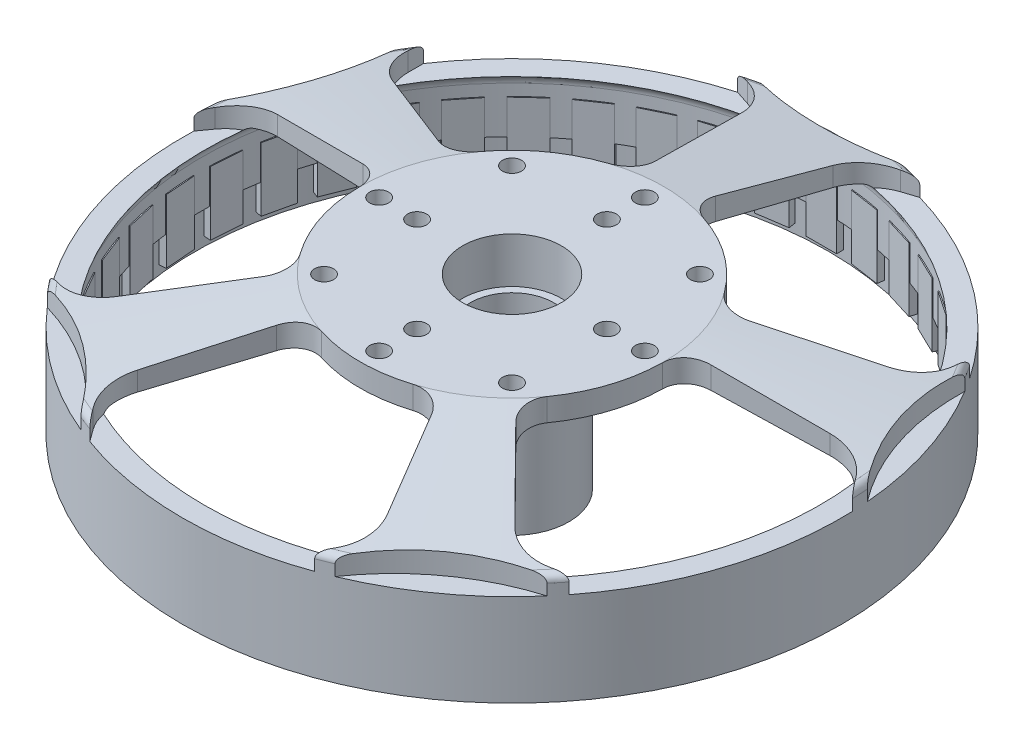
SolidWorks part; units mm, degrees
ref_plane "Front Plane" through (0, 0, 0) normal (0, 0, 1) x (1, 0, 0)
ref_plane "Top Plane" through (0, 0, 0) normal (0, 1, 0) x (1, 0, 0)
ref_plane "Right Plane" through (0, 0, 0) normal (1, 0, 0) x (0, 0, -1)
sketch "Sketch2" plane through (0, 0, 0) normal (0, 0, 1) x (1, 0, 0)
  line L0 (0, 0) -> (0, -18.25) construction
  line L1 (0, -18.25) -> (43.4, -18.25) construction
  line L2 (43.4, -18.25) -> (43.4, -6.1)
  line L3 (20, -3) -> (8.5, -3)
  line L4 (40.9, -5.8) -> (40.9, -13.25)
  line L5 (40.9, -13.25) -> (41.7, -13.25)
  line L6 (41.7, -13.25) -> (41.7, -18.25)
  line L7 (41.7, -18.25) -> (43.4, -18.25)
  line L8 (20, 0) -> (6.5, 0)
  line L9 (20, 0) -> (43.4, -3.8)
  line L10 (43.4, -3.8) -> (43.4, -6.1)
  line L12 (8.5, -3) -> (8.5, -8)
  line L13 (20, -3) -> (40.9, -5.8)
  line L14 (8.5, -8) -> (7.5, -8)
  line L15 (7.5, -8) -> (7.5, -24.5)
  line L16 (7.5, -24.5) -> (3.5, -24.5)
  line L17 (3.5, -24.5) -> (3.5, -19.5)
  line L18 (3.5, -19.5) -> (5.5, -19.5)
  line L19 (5.5, -19.5) -> (5.5, -6)
  line L20 (5.5, -6) -> (6.5, -6)
  line L21 (6.5, -6) -> (6.5, 0)
  dimension "D1" = 18.25
  dimension "D2" = 43.4
  dimension "D3" = 12.15
  dimension "D4" = 1.7
  dimension "D5" = 5
  dimension "D6" = 2.5
  dimension "D7" = 3
  dimension "D8" = 2.3
  dimension "D9" = 20
  dimension "D10" = 2
  dimension "D11" = 24.5
  dimension "D12" = 7.5
  dimension "D13" = 3.5
  dimension "D14" = 5.5
  dimension "D15" = 6.5
  dimension "D16" = 8.5
  dimension "D17" = 6
  dimension "D18" = 5
  dimension "D19" = 19.5
revolve "Revolve1" add sketch "Sketch2" angle 360 about L0
fillet "Fillet1" radius 1 1 edges at (0, -3.8, 43.4)
fillet "Fillet2" radius 1.5 1 edges at (0, -5.8, 40.9)
fillet "Fillet3" radius 0.5 1 edges at (0, -19.5, 5.5)
sketch "Sketch3" plane through (0, 0, 0) normal (0, 1, 0) x (1, 0, 0)
  line L0 (0, 0) -> (0, -43.4) construction
  line L1 (0, 0) -> (-25.5099, -35.1113) construction
  line L2 (0, 0) -> (-41.2759, -13.4113) construction
  line L3 (0, 0) -> (-41.2759, 13.4113) construction
  line L4 (0, 0) -> (-25.5099, 35.1113) construction
  line L5 (0, 0) -> (0, 43.4) construction
  line L6 (0, 0) -> (25.5099, 35.1113) construction
  line L7 (0, 0) -> (41.2759, 13.4113) construction
  line L8 (0, 0) -> (41.2759, -13.4113) construction
  line L9 (0, 0) -> (25.5099, -35.1113) construction
  line L10 (7, 42.8318) -> (3.5, 19.6914) construction
  line L11 (17.646, 9.4137) -> (38.5723, 19.8931) construction
  line L12 (3.9727, 22.8168) -> (6.0087, 36.2774)
  line L13 (20.4724, 10.8291) -> (32.6451, 16.9249)
  line L14 (10.0871, 41.0865) -> (12, 41.708)
  line L15 (35.9585, 22.2898) -> (35.9585, 24.3012)
  line L16 (22.9277, 3.2725) -> (36.3587, 5.4958)
  line L17 (16.6254, -16.1241) -> (26.1845, -25.8173)
  line L18 (42.1926, 3.103) -> (43.3749, 1.4758)
  line L19 (32.3106, -27.3106) -> (34.2236, -26.6891)
  line L20 (10.1974, -20.7943) -> (16.4622, -32.8809)
  line L21 (-10.1974, -20.7943) -> (-16.4622, -32.8809)
  line L22 (15.9894, -39.1687) -> (14.8072, -40.7959)
  line L23 (-15.9894, -39.1687) -> (-14.8072, -40.7959)
  line L24 (-16.6254, -16.1241) -> (-26.1845, -25.8173)
  line L25 (-22.9277, 3.2725) -> (-36.3587, 5.4958)
  line L26 (-32.3106, -27.3106) -> (-34.2236, -26.6891)
  line L27 (-42.1926, 3.103) -> (-43.3749, 1.4758)
  line L28 (-20.4724, 10.8291) -> (-32.6451, 16.9249)
  line L29 (-3.9727, 22.8168) -> (-6.0087, 36.2774)
  line L30 (-35.9585, 22.2898) -> (-35.9585, 24.3012)
  line L31 (-10.0871, 41.0865) -> (-12, 41.708)
  circle A0 centre (0, 0) radius 43.4 construction
  arc A1 (3.5, 19.6914) -> (17.646, 9.4137) centre (0, 0) cw construction
  arc A3 (7, 42.8318) -> (38.5723, 19.8931) centre (0, 0) cw construction
  arc A4 (6.3263, 18.9731) -> (16.0896, 11.8796) centre (0, 0) cw
  arc A5 (6.3263, 18.9731) -> (3.9727, 22.8168) centre (7.4334, 22.2934) cw
  arc A6 (16.0896, 11.8796) -> (20.4724, 10.8291) centre (18.9052, 13.9586) ccw
  arc A7 (6.0087, 36.2774) -> (10.0871, 41.0865) centre (11.9412, 35.3801) cw
  arc A8 (32.6451, 16.9249) -> (35.9585, 22.2898) centre (29.9585, 22.2898) ccw
  arc A9 (12, 41.708) -> (35.9585, 24.3012) centre (0, 0) cw
  arc A10 (19.9994, -0.1536) -> (16.2702, -11.6311) centre (0, 0) cw
  arc A11 (16.2702, -11.6311) -> (16.6254, -16.1241) centre (19.1174, -13.6665) ccw
  arc A12 (36.3587, 5.4958) -> (42.1926, 3.103) centre (37.3385, -0.4237) cw
  arc A13 (26.1845, -25.8173) -> (32.3106, -27.3106) centre (30.4565, -21.6043) ccw
  arc A14 (43.3749, 1.4758) -> (34.2236, -26.6891) centre (0, 0) cw
  arc A15 (19.9994, -0.1536) -> (22.9277, 3.2725) centre (23.4993, -0.1805) cw
  arc A16 (6.034, -19.068) -> (-6.034, -19.068) centre (0, 0) cw
  arc A17 (-6.034, -19.068) -> (-10.1974, -20.7943) centre (-7.09, -22.405) ccw
  arc A18 (16.4622, -32.8809) -> (15.9894, -39.1687) centre (11.1353, -35.642) cw
  arc A19 (-16.4622, -32.8809) -> (-15.9894, -39.1687) centre (-11.1353, -35.642) ccw
  arc A20 (14.8072, -40.7959) -> (-14.8072, -40.7959) centre (0, 0) cw
  arc A21 (6.034, -19.068) -> (10.1974, -20.7943) centre (7.09, -22.405) cw
  arc A22 (-16.2702, -11.6311) -> (-19.9994, -0.1536) centre (0, 0) cw
  arc A23 (-19.9994, -0.1536) -> (-22.9277, 3.2725) centre (-23.4993, -0.1805) ccw
  arc A24 (-26.1845, -25.8173) -> (-32.3106, -27.3106) centre (-30.4565, -21.6043) cw
  arc A25 (-36.3587, 5.4958) -> (-42.1926, 3.103) centre (-37.3385, -0.4237) ccw
  arc A26 (-34.2236, -26.6891) -> (-43.3749, 1.4758) centre (0, 0) cw
  arc A27 (-16.2702, -11.6311) -> (-16.6254, -16.1241) centre (-19.1174, -13.6665) cw
  arc A28 (-16.0896, 11.8796) -> (-6.3263, 18.9731) centre (0, 0) cw
  arc A29 (-6.3263, 18.9731) -> (-3.9727, 22.8168) centre (-7.4334, 22.2934) ccw
  arc A30 (-32.6451, 16.9249) -> (-35.9585, 22.2898) centre (-29.9585, 22.2898) cw
  arc A31 (-6.0087, 36.2774) -> (-10.0871, 41.0865) centre (-11.9412, 35.3801) ccw
  arc A32 (-35.9585, 24.3012) -> (-12, 41.708) centre (0, 0) cw
  arc A33 (-16.0896, 11.8796) -> (-20.4724, 10.8291) centre (-18.9052, 13.9586) cw
  circle A34 centre (0, 0) radius 20 construction
  point P17 (0, 0)
  point P95 (0, 0)
  dimension "D4" = 3.5
  dimension "D5" = 6
  dimension "D2" = 3.5
  dimension "D3" = 7
  dimension "D6" = 12
  dimension "D1" = 10
  dimension "D7" = 5
extrude "Cut-Extrude2" cut sketch "Sketch3" against normal offset from surface (6.1 mm away) 12.15 up to face at (0, -18.25, 43.4)
sketch "Sketch4" plane through (0, 0, 0) normal (0, 1, 0) x (1, 0, 0)
  line L0 (0, 0) -> (0, 70.5165) construction
  line L1 (-10, 42.2322) -> (10, 42.2322) construction
  line L2 (0, 0) -> (67.0652, 21.7908) construction
  line L3 (0, 0) -> (41.4486, -57.049) construction
  line L4 (0, 0) -> (-41.4486, -57.049) construction
  line L5 (0, 0) -> (-67.0652, 21.7908) construction
  circle A0 centre (0, 70.5165) radius 30
  arc A1 (-34.2236, 26.6891) -> (-12, 41.708) centre (0, 0) ccw construction
  circle A2 centre (67.0652, 21.7908) radius 30
  circle A3 centre (41.4486, -57.049) radius 30
  circle A4 centre (-41.4486, -57.049) radius 30
  circle A5 centre (-67.0652, 21.7908) radius 30
  point P20 (0, 0)
  dimension "D1" = 60
  dimension "D2" = 20
  dimension "D3" = 5
extrude "Cut-Extrude3" cut sketch "Sketch4" against normal offset from surface (6.1 mm away) 12.15 up to face at (0, -18.25, 43.4)
sketch "Sketch6" plane through (0, -13.25, 0) normal (0, -1, 0) x (1, 0, 0)
  line L0 (0, 0) -> (0, -41.202) construction
  line L1 (-4.0961, -40.5949) -> (-8.0514, -39.9988)
  line L2 (2, -40.752) -> (-2, -40.752)
  line L3 (2, -40.752) -> (2, -41.652)
  line L4 (2, -41.652) -> (-2, -41.652) construction
  line L5 (-2, -40.752) -> (-2, -41.652)
  line L6 (2, -40.752) -> (-2, -41.652) construction
  line L7 (2, -41.652) -> (-2, -40.752) construction
  line L8 (-4.0961, -40.5949) -> (-4.2302, -41.4849)
  line L9 (-8.0514, -39.9988) -> (-8.1856, -40.8887)
  line L10 (-4.2302, -41.4849) -> (-8.1856, -40.8887) construction
  line L11 (-4.0961, -40.5949) -> (-8.1856, -40.8887) construction
  line L12 (-4.2302, -41.4849) -> (-8.0514, -39.9988) construction
  line L13 (-10.1007, -39.531) -> (-13.923, -38.352)
  line L14 (-10.1007, -39.531) -> (-10.366, -40.391)
  line L15 (-13.923, -38.352) -> (-14.1883, -39.212)
  line L16 (-10.366, -40.391) -> (-14.1883, -39.212) construction
  line L17 (-10.1007, -39.531) -> (-14.1883, -39.212) construction
  line L18 (-10.366, -40.391) -> (-13.923, -38.352) construction
  line L19 (-15.8797, -37.5841) -> (-19.4836, -35.8485)
  line L20 (-15.8797, -37.5841) -> (-16.2702, -38.3949)
  line L21 (-19.4836, -35.8485) -> (-19.8741, -36.6594)
  line L22 (-16.2702, -38.3949) -> (-19.8741, -36.6594) construction
  line L23 (-15.8797, -37.5841) -> (-19.8741, -36.6594) construction
  line L24 (-16.2702, -38.3949) -> (-19.4836, -35.8485) construction
  line L25 (-21.3039, -34.7975) -> (-24.6089, -32.5443)
  line L26 (-21.3039, -34.7975) -> (-21.8109, -35.5411)
  line L27 (-24.6089, -32.5443) -> (-25.1159, -33.2879)
  line L28 (-21.8109, -35.5411) -> (-25.1159, -33.2879) construction
  line L29 (-21.3039, -34.7975) -> (-25.1159, -33.2879) construction
  line L30 (-21.8109, -35.5411) -> (-24.6089, -32.5443) construction
  line L31 (-26.2523, -31.2337) -> (-29.1845, -28.513)
  line L32 (-26.2523, -31.2337) -> (-26.8645, -31.8934)
  line L33 (-29.1845, -28.513) -> (-29.7967, -29.1727)
  line L34 (-26.8645, -31.8934) -> (-29.7967, -29.1727) construction
  line L35 (-26.2523, -31.2337) -> (-29.7967, -29.1727) construction
  line L36 (-26.8645, -31.8934) -> (-29.1845, -28.513) construction
  line L37 (-30.6142, -26.9721) -> (-33.1082, -23.8448)
  line L38 (-30.6142, -26.9721) -> (-31.3179, -27.5333)
  line L39 (-33.1082, -23.8448) -> (-33.8118, -24.4059)
  line L40 (-31.3179, -27.5333) -> (-33.8118, -24.4059) construction
  line L41 (-30.6142, -26.9721) -> (-33.8118, -24.4059) construction
  line L42 (-31.3179, -27.5333) -> (-33.1082, -23.8448) construction
  line L43 (-34.2923, -22.1081) -> (-36.2923, -18.644)
  line L44 (-34.2923, -22.1081) -> (-35.0717, -22.5581)
  line L45 (-36.2923, -18.644) -> (-37.0717, -19.094)
  line L46 (-35.0717, -22.5581) -> (-37.0717, -19.094) construction
  line L47 (-34.2923, -22.1081) -> (-37.0717, -19.094) construction
  line L48 (-35.0717, -22.5581) -> (-36.2923, -18.644) construction
  line L49 (-37.2043, -16.7501) -> (-38.6657, -13.0266)
  line L50 (-37.2043, -16.7501) -> (-38.0421, -17.0789)
  line L51 (-38.6657, -13.0266) -> (-39.5034, -13.3554)
  line L52 (-38.0421, -17.0789) -> (-39.5034, -13.3554) construction
  line L53 (-37.2043, -16.7501) -> (-39.5034, -13.3554) construction
  line L54 (-38.0421, -17.0789) -> (-38.6657, -13.0266) construction
  line L55 (-39.2852, -11.018) -> (-40.1753, -7.1183)
  line L56 (-39.2852, -11.018) -> (-40.1627, -11.2183)
  line L57 (-40.1753, -7.1183) -> (-41.0527, -7.3186)
  line L58 (-40.1627, -11.2183) -> (-41.0527, -7.3186) construction
  line L59 (-39.2852, -11.018) -> (-41.0527, -7.3186) construction
  line L60 (-40.1627, -11.2183) -> (-40.1753, -7.1183) construction
  line L61 (-40.4886, -5.0398) -> (-40.7875, -1.051)
  line L62 (-40.4886, -5.0398) -> (-41.3861, -5.1071)
  line L63 (-40.7875, -1.051) -> (-41.685, -1.1183)
  line L64 (-41.3861, -5.1071) -> (-41.685, -1.1183) construction
  line L65 (-40.4886, -5.0398) -> (-41.685, -1.1183) construction
  line L66 (-41.3861, -5.1071) -> (-40.7875, -1.051) construction
  line L67 (-40.7875, 1.051) -> (-40.4886, 5.0398)
  line L68 (-40.7875, 1.051) -> (-41.685, 1.1183)
  line L69 (-40.4886, 5.0398) -> (-41.3861, 5.1071)
  line L70 (-41.685, 1.1183) -> (-41.3861, 5.1071) construction
  line L71 (-40.7875, 1.051) -> (-41.3861, 5.1071) construction
  line L72 (-41.685, 1.1183) -> (-40.4886, 5.0398) construction
  line L73 (-40.1753, 7.1183) -> (-39.2852, 11.018)
  line L74 (-40.1753, 7.1183) -> (-41.0527, 7.3186)
  line L75 (-39.2852, 11.018) -> (-40.1627, 11.2183)
  line L76 (-41.0527, 7.3186) -> (-40.1627, 11.2183) construction
  line L77 (-40.1753, 7.1183) -> (-40.1627, 11.2183) construction
  line L78 (-41.0527, 7.3186) -> (-39.2852, 11.018) construction
  line L79 (-38.6657, 13.0266) -> (-37.2043, 16.7501)
  line L80 (-38.6657, 13.0266) -> (-39.5034, 13.3554)
  line L81 (-37.2043, 16.7501) -> (-38.0421, 17.0789)
  line L82 (-39.5034, 13.3554) -> (-38.0421, 17.0789) construction
  line L83 (-38.6657, 13.0266) -> (-38.0421, 17.0789) construction
  line L84 (-39.5034, 13.3554) -> (-37.2043, 16.7501) construction
  line L85 (-36.2923, 18.644) -> (-34.2923, 22.1081)
  line L86 (-36.2923, 18.644) -> (-37.0717, 19.094)
  line L87 (-34.2923, 22.1081) -> (-35.0717, 22.5581)
  line L88 (-37.0717, 19.094) -> (-35.0717, 22.5581) construction
  line L89 (-36.2923, 18.644) -> (-35.0717, 22.5581) construction
  line L90 (-37.0717, 19.094) -> (-34.2923, 22.1081) construction
  line L91 (-33.1082, 23.8448) -> (-30.6142, 26.9721)
  line L92 (-33.1082, 23.8448) -> (-33.8118, 24.4059)
  line L93 (-30.6142, 26.9721) -> (-31.3179, 27.5333)
  line L94 (-33.8118, 24.4059) -> (-31.3179, 27.5333) construction
  line L95 (-33.1082, 23.8448) -> (-31.3179, 27.5333) construction
  line L96 (-33.8118, 24.4059) -> (-30.6142, 26.9721) construction
  line L97 (-29.1845, 28.513) -> (-26.2523, 31.2337)
  line L98 (-29.1845, 28.513) -> (-29.7967, 29.1727)
  line L99 (-26.2523, 31.2337) -> (-26.8645, 31.8934)
  line L100 (-29.7967, 29.1727) -> (-26.8645, 31.8934) construction
  line L101 (-29.1845, 28.513) -> (-26.8645, 31.8934) construction
  line L102 (-29.7967, 29.1727) -> (-26.2523, 31.2337) construction
  line L103 (-24.6089, 32.5443) -> (-21.3039, 34.7975)
  line L104 (-24.6089, 32.5443) -> (-25.1159, 33.2879)
  line L105 (-21.3039, 34.7975) -> (-21.8109, 35.5411)
  line L106 (-25.1159, 33.2879) -> (-21.8109, 35.5411) construction
  line L107 (-24.6089, 32.5443) -> (-21.8109, 35.5411) construction
  line L108 (-25.1159, 33.2879) -> (-21.3039, 34.7975) construction
  line L109 (-19.4836, 35.8485) -> (-15.8797, 37.5841)
  line L110 (-19.4836, 35.8485) -> (-19.8741, 36.6594)
  line L111 (-15.8797, 37.5841) -> (-16.2702, 38.3949)
  line L112 (-19.8741, 36.6594) -> (-16.2702, 38.3949) construction
  line L113 (-19.4836, 35.8485) -> (-16.2702, 38.3949) construction
  line L114 (-19.8741, 36.6594) -> (-15.8797, 37.5841) construction
  line L115 (-13.923, 38.352) -> (-10.1007, 39.531)
  line L116 (-13.923, 38.352) -> (-14.1883, 39.212)
  line L117 (-10.1007, 39.531) -> (-10.366, 40.391)
  line L118 (-14.1883, 39.212) -> (-10.366, 40.391) construction
  line L119 (-13.923, 38.352) -> (-10.366, 40.391) construction
  line L120 (-14.1883, 39.212) -> (-10.1007, 39.531) construction
  line L121 (-8.0514, 39.9988) -> (-4.0961, 40.5949)
  line L122 (-8.0514, 39.9988) -> (-8.1856, 40.8887)
  line L123 (-4.0961, 40.5949) -> (-4.2302, 41.4849)
  line L124 (-8.1856, 40.8887) -> (-4.2302, 41.4849) construction
  line L125 (-8.0514, 39.9988) -> (-4.2302, 41.4849) construction
  line L126 (-8.1856, 40.8887) -> (-4.0961, 40.5949) construction
  line L127 (-2, 40.752) -> (2, 40.752)
  line L128 (-2, 40.752) -> (-2, 41.652)
  line L129 (2, 40.752) -> (2, 41.652)
  line L130 (-2, 41.652) -> (2, 41.652) construction
  line L131 (-2, 40.752) -> (2, 41.652) construction
  line L132 (-2, 41.652) -> (2, 40.752) construction
  line L133 (4.0961, 40.5949) -> (8.0514, 39.9988)
  line L134 (4.0961, 40.5949) -> (4.2302, 41.4849)
  line L135 (8.0514, 39.9988) -> (8.1856, 40.8887)
  line L136 (4.2302, 41.4849) -> (8.1856, 40.8887) construction
  line L137 (4.0961, 40.5949) -> (8.1856, 40.8887) construction
  line L138 (4.2302, 41.4849) -> (8.0514, 39.9988) construction
  line L139 (10.1007, 39.531) -> (13.923, 38.352)
  line L140 (10.1007, 39.531) -> (10.366, 40.391)
  line L141 (13.923, 38.352) -> (14.1883, 39.212)
  line L142 (10.366, 40.391) -> (14.1883, 39.212) construction
  line L143 (10.1007, 39.531) -> (14.1883, 39.212) construction
  line L144 (10.366, 40.391) -> (13.923, 38.352) construction
  line L145 (15.8797, 37.5841) -> (19.4836, 35.8485)
  line L146 (15.8797, 37.5841) -> (16.2702, 38.3949)
  line L147 (19.4836, 35.8485) -> (19.8741, 36.6594)
  line L148 (16.2702, 38.3949) -> (19.8741, 36.6594) construction
  line L149 (15.8797, 37.5841) -> (19.8741, 36.6594) construction
  line L150 (16.2702, 38.3949) -> (19.4836, 35.8485) construction
  line L151 (21.3039, 34.7975) -> (24.6089, 32.5443)
  line L152 (21.3039, 34.7975) -> (21.8109, 35.5411)
  line L153 (24.6089, 32.5443) -> (25.1159, 33.2879)
  line L154 (21.8109, 35.5411) -> (25.1159, 33.2879) construction
  line L155 (21.3039, 34.7975) -> (25.1159, 33.2879) construction
  line L156 (21.8109, 35.5411) -> (24.6089, 32.5443) construction
  line L157 (26.2523, 31.2337) -> (29.1845, 28.513)
  line L158 (26.2523, 31.2337) -> (26.8645, 31.8934)
  line L159 (29.1845, 28.513) -> (29.7967, 29.1727)
  line L160 (26.8645, 31.8934) -> (29.7967, 29.1727) construction
  line L161 (26.2523, 31.2337) -> (29.7967, 29.1727) construction
  line L162 (26.8645, 31.8934) -> (29.1845, 28.513) construction
  line L163 (30.6142, 26.9721) -> (33.1082, 23.8448)
  line L164 (30.6142, 26.9721) -> (31.3179, 27.5333)
  line L165 (33.1082, 23.8448) -> (33.8118, 24.4059)
  line L166 (31.3179, 27.5333) -> (33.8118, 24.4059) construction
  line L167 (30.6142, 26.9721) -> (33.8118, 24.4059) construction
  line L168 (31.3179, 27.5333) -> (33.1082, 23.8448) construction
  line L169 (34.2923, 22.1081) -> (36.2923, 18.644)
  line L170 (34.2923, 22.1081) -> (35.0717, 22.5581)
  line L171 (36.2923, 18.644) -> (37.0717, 19.094)
  line L172 (35.0717, 22.5581) -> (37.0717, 19.094) construction
  line L173 (34.2923, 22.1081) -> (37.0717, 19.094) construction
  line L174 (35.0717, 22.5581) -> (36.2923, 18.644) construction
  line L175 (37.2043, 16.7501) -> (38.6657, 13.0266)
  line L176 (37.2043, 16.7501) -> (38.0421, 17.0789)
  line L177 (38.6657, 13.0266) -> (39.5034, 13.3554)
  line L178 (38.0421, 17.0789) -> (39.5034, 13.3554) construction
  line L179 (37.2043, 16.7501) -> (39.5034, 13.3554) construction
  line L180 (38.0421, 17.0789) -> (38.6657, 13.0266) construction
  line L181 (39.2852, 11.018) -> (40.1753, 7.1183)
  line L182 (39.2852, 11.018) -> (40.1627, 11.2183)
  line L183 (40.1753, 7.1183) -> (41.0527, 7.3186)
  line L184 (40.1627, 11.2183) -> (41.0527, 7.3186) construction
  line L185 (39.2852, 11.018) -> (41.0527, 7.3186) construction
  line L186 (40.1627, 11.2183) -> (40.1753, 7.1183) construction
  line L187 (40.4886, 5.0398) -> (40.7875, 1.051)
  line L188 (40.4886, 5.0398) -> (41.3861, 5.1071)
  line L189 (40.7875, 1.051) -> (41.685, 1.1183)
  line L190 (41.3861, 5.1071) -> (41.685, 1.1183) construction
  line L191 (40.4886, 5.0398) -> (41.685, 1.1183) construction
  line L192 (41.3861, 5.1071) -> (40.7875, 1.051) construction
  line L193 (40.7875, -1.051) -> (40.4886, -5.0398)
  line L194 (40.7875, -1.051) -> (41.685, -1.1183)
  line L195 (40.4886, -5.0398) -> (41.3861, -5.1071)
  line L196 (41.685, -1.1183) -> (41.3861, -5.1071) construction
  line L197 (40.7875, -1.051) -> (41.3861, -5.1071) construction
  line L198 (41.685, -1.1183) -> (40.4886, -5.0398) construction
  line L199 (40.1753, -7.1183) -> (39.2852, -11.018)
  line L200 (40.1753, -7.1183) -> (41.0527, -7.3186)
  line L201 (39.2852, -11.018) -> (40.1627, -11.2183)
  line L202 (41.0527, -7.3186) -> (40.1627, -11.2183) construction
  line L203 (40.1753, -7.1183) -> (40.1627, -11.2183) construction
  line L204 (41.0527, -7.3186) -> (39.2852, -11.018) construction
  line L205 (38.6657, -13.0266) -> (37.2043, -16.7501)
  line L206 (38.6657, -13.0266) -> (39.5034, -13.3554)
  line L207 (37.2043, -16.7501) -> (38.0421, -17.0789)
  line L208 (39.5034, -13.3554) -> (38.0421, -17.0789) construction
  line L209 (38.6657, -13.0266) -> (38.0421, -17.0789) construction
  line L210 (39.5034, -13.3554) -> (37.2043, -16.7501) construction
  line L211 (36.2923, -18.644) -> (34.2923, -22.1081)
  line L212 (36.2923, -18.644) -> (37.0717, -19.094)
  line L213 (34.2923, -22.1081) -> (35.0717, -22.5581)
  line L214 (37.0717, -19.094) -> (35.0717, -22.5581) construction
  line L215 (36.2923, -18.644) -> (35.0717, -22.5581) construction
  line L216 (37.0717, -19.094) -> (34.2923, -22.1081) construction
  line L217 (33.1082, -23.8448) -> (30.6142, -26.9721)
  line L218 (33.1082, -23.8448) -> (33.8118, -24.4059)
  line L219 (30.6142, -26.9721) -> (31.3179, -27.5333)
  line L220 (33.8118, -24.4059) -> (31.3179, -27.5333) construction
  line L221 (33.1082, -23.8448) -> (31.3179, -27.5333) construction
  line L222 (33.8118, -24.4059) -> (30.6142, -26.9721) construction
  line L223 (29.1845, -28.513) -> (26.2523, -31.2337)
  line L224 (29.1845, -28.513) -> (29.7967, -29.1727)
  line L225 (26.2523, -31.2337) -> (26.8645, -31.8934)
  line L226 (29.7967, -29.1727) -> (26.8645, -31.8934) construction
  line L227 (29.1845, -28.513) -> (26.8645, -31.8934) construction
  line L228 (29.7967, -29.1727) -> (26.2523, -31.2337) construction
  line L229 (24.6089, -32.5443) -> (21.3039, -34.7975)
  line L230 (24.6089, -32.5443) -> (25.1159, -33.2879)
  line L231 (21.3039, -34.7975) -> (21.8109, -35.5411)
  line L232 (25.1159, -33.2879) -> (21.8109, -35.5411) construction
  line L233 (24.6089, -32.5443) -> (21.8109, -35.5411) construction
  line L234 (25.1159, -33.2879) -> (21.3039, -34.7975) construction
  line L235 (19.4836, -35.8485) -> (15.8797, -37.5841)
  line L236 (19.4836, -35.8485) -> (19.8741, -36.6594)
  line L237 (15.8797, -37.5841) -> (16.2702, -38.3949)
  line L238 (19.8741, -36.6594) -> (16.2702, -38.3949) construction
  line L239 (19.4836, -35.8485) -> (16.2702, -38.3949) construction
  line L240 (19.8741, -36.6594) -> (15.8797, -37.5841) construction
  line L241 (13.923, -38.352) -> (10.1007, -39.531)
  line L242 (13.923, -38.352) -> (14.1883, -39.212)
  line L243 (10.1007, -39.531) -> (10.366, -40.391)
  line L244 (14.1883, -39.212) -> (10.366, -40.391) construction
  line L245 (13.923, -38.352) -> (10.366, -40.391) construction
  line L246 (14.1883, -39.212) -> (10.1007, -39.531) construction
  line L247 (8.0514, -39.9988) -> (4.0961, -40.5949)
  line L248 (8.0514, -39.9988) -> (8.1856, -40.8887)
  line L249 (4.0961, -40.5949) -> (4.2302, -41.4849)
  line L250 (8.1856, -40.8887) -> (4.2302, -41.4849) construction
  line L251 (8.0514, -39.9988) -> (4.2302, -41.4849) construction
  line L252 (8.1856, -40.8887) -> (4.0961, -40.5949) construction
  arc A0 (2, -41.652) -> (-2, -41.652) centre (0, 0) cw
  circle A1 centre (0, 0) radius 41.7 construction
  arc A2 (-4.2302, -41.4849) -> (-8.1856, -40.8887) centre (0, 0) cw
  arc A3 (-10.366, -40.391) -> (-14.1883, -39.212) centre (0, 0) cw
  arc A4 (-16.2702, -38.3949) -> (-19.8741, -36.6594) centre (0, 0) cw
  arc A5 (-21.8109, -35.5411) -> (-25.1159, -33.2879) centre (0, 0) cw
  arc A6 (-26.8645, -31.8934) -> (-29.7967, -29.1727) centre (0, 0) cw
  arc A7 (-31.3179, -27.5333) -> (-33.8118, -24.4059) centre (0, 0) cw
  arc A8 (-35.0717, -22.5581) -> (-37.0717, -19.094) centre (0, 0) cw
  arc A9 (-38.0421, -17.0789) -> (-39.5034, -13.3554) centre (0, 0) cw
  arc A10 (-40.1627, -11.2183) -> (-41.0527, -7.3186) centre (0, 0) cw
  arc A11 (-41.3861, -5.1071) -> (-41.685, -1.1183) centre (0, 0) cw
  arc A12 (-41.685, 1.1183) -> (-41.3861, 5.1071) centre (0, 0) cw
  arc A13 (-41.0527, 7.3186) -> (-40.1627, 11.2183) centre (0, 0) cw
  arc A14 (-39.5034, 13.3554) -> (-38.0421, 17.0789) centre (0, 0) cw
  arc A15 (-37.0717, 19.094) -> (-35.0717, 22.5581) centre (0, 0) cw
  arc A16 (-33.8118, 24.4059) -> (-31.3179, 27.5333) centre (0, 0) cw
  arc A17 (-29.7967, 29.1727) -> (-26.8645, 31.8934) centre (0, 0) cw
  arc A18 (-25.1159, 33.2879) -> (-21.8109, 35.5411) centre (0, 0) cw
  arc A19 (-19.8741, 36.6594) -> (-16.2702, 38.3949) centre (0, 0) cw
  arc A20 (-14.1883, 39.212) -> (-10.366, 40.391) centre (0, 0) cw
  arc A21 (-8.1856, 40.8887) -> (-4.2302, 41.4849) centre (0, 0) cw
  arc A22 (-2, 41.652) -> (2, 41.652) centre (0, 0) cw
  arc A23 (4.2302, 41.4849) -> (8.1856, 40.8887) centre (0, 0) cw
  arc A24 (10.366, 40.391) -> (14.1883, 39.212) centre (0, 0) cw
  arc A25 (16.2702, 38.3949) -> (19.8741, 36.6594) centre (0, 0) cw
  arc A26 (21.8109, 35.5411) -> (25.1159, 33.2879) centre (0, 0) cw
  arc A27 (26.8645, 31.8934) -> (29.7967, 29.1727) centre (0, 0) cw
  arc A28 (31.3179, 27.5333) -> (33.8118, 24.4059) centre (0, 0) cw
  arc A29 (35.0717, 22.5581) -> (37.0717, 19.094) centre (0, 0) cw
  arc A30 (38.0421, 17.0789) -> (39.5034, 13.3554) centre (0, 0) cw
  arc A31 (40.1627, 11.2183) -> (41.0527, 7.3186) centre (0, 0) cw
  arc A32 (41.3861, 5.1071) -> (41.685, 1.1183) centre (0, 0) cw
  arc A33 (41.685, -1.1183) -> (41.3861, -5.1071) centre (0, 0) cw
  arc A34 (41.0527, -7.3186) -> (40.1627, -11.2183) centre (0, 0) cw
  arc A35 (39.5034, -13.3554) -> (38.0421, -17.0789) centre (0, 0) cw
  arc A36 (37.0717, -19.094) -> (35.0717, -22.5581) centre (0, 0) cw
  arc A37 (33.8118, -24.4059) -> (31.3179, -27.5333) centre (0, 0) cw
  arc A38 (29.7967, -29.1727) -> (26.8645, -31.8934) centre (0, 0) cw
  arc A39 (25.1159, -33.2879) -> (21.8109, -35.5411) centre (0, 0) cw
  arc A40 (19.8741, -36.6594) -> (16.2702, -38.3949) centre (0, 0) cw
  arc A41 (14.1883, -39.212) -> (10.366, -40.391) centre (0, 0) cw
  arc A42 (8.1856, -40.8887) -> (4.2302, -41.4849) centre (0, 0) cw
  point P177 (0, 0)
  dimension "D1" = 0.9
  dimension "D2" = 4
  dimension "D3" = 42
extrude "Boss-Extrude6" add sketch "Sketch6" along normal blind 3.8 and the other way blind 4.6
hole_wizard "Tap Drill for M3x0.5 Tap1" positions "Sketch11" profile "Sketch10" hole size "M3x0.5" standard "ANSI Metric" end condition through all
sketch "Sketch11" plane through (0, 0, 0) normal (0, 1, 0) x (1, 0, 0)
  point P0 (0, 17.5)
  point P7 (12.3744, 12.3744)
  point P8 (17.5, 0)
  point P9 (12.3744, -12.3744)
  point P10 (0, -17.5)
  point P11 (-12.3744, -12.3744)
  point P12 (-17.5, 0)
  point P13 (-12.3744, 12.3744)
  dimension "D2" = 17.5
  dimension "D3" = 17.5
  dimension "D1" = 8
sketch "Sketch10" plane through (0, 0, -17.5) normal (1, 0, 0) x (0, 0, 1)
  line L0 (0, 0) -> (0, 24.5)
  line L1 (0, 24.5) -> (1.25, 24.5)
  line L2 (1.25, 24.5) -> (1.25, 0)
  line L5 (1.25, 0) -> (0, 0)
  line L11 (0, -6.35) -> (0, 107.95) construction
  dimension "Thru Hole Dia." = 2.5
  dimension "Thru Hole Depth" = 24.5
hole_wizard "Tap Drill for M3x0.5 Tap2" positions "Sketch12" profile "Sketch13" hole size "M3x0.5" standard "ANSI Metric" end condition through all
sketch "Sketch12" plane through (0, 0, 0) normal (0, 1, 0) x (1, 0, 0)
  point P0 (0, 12.5)
  point P6 (12.5, 0)
  point P7 (0, -12.5)
  point P8 (-12.5, 0)
  dimension "D2" = 12.5
  dimension "D1" = 4
sketch "Sketch13" plane through (0, 0, -12.5) normal (1, 0, 0) x (0, 0, 1)
  line L0 (0, 0) -> (0, 24.5)
  line L1 (0, 24.5) -> (1.25, 24.5)
  line L2 (1.25, 24.5) -> (1.25, 0)
  line L5 (1.25, 0) -> (0, 0)
  line L11 (0, -6.35) -> (0, 107.95) construction
  dimension "Thru Hole Dia." = 2.5
  dimension "Thru Hole Depth" = 24.5
hole_wizard "Tap Drill for M3x0.5 Tap3" positions "Sketch14" profile "Sketch15" hole size "M3x0.5" standard "ANSI Metric"
sketch "Sketch14" plane through (0, -24.5, 0) normal (0, -1, 0) x (-1, 0, 0)
  point P0 (0, -5.5)
  point P2 (0, 5.5)
  dimension "D1" = 5.5
  dimension "D2" = 5.5
sketch "Sketch15" plane through (0, -24.5, 5.5) normal (1, 0, 0) x (0, 0, -1)
  line L0 (0, 0) -> (0, 6.7511)
  line L1 (0, 6.7511) -> (1.25, 6)
  line L2 (1.25, 6) -> (1.25, 0)
  line L5 (1.25, 0) -> (0, 0)
  line L10 (0, 6.7511) -> (-1.25, 6) construction
  line L11 (0, -6.35) -> (0, 107.95) construction
  dimension "Hole Dia." = 2.5
  dimension "Hole Depth" = 6
  dimension "Drill Angle" = 118
